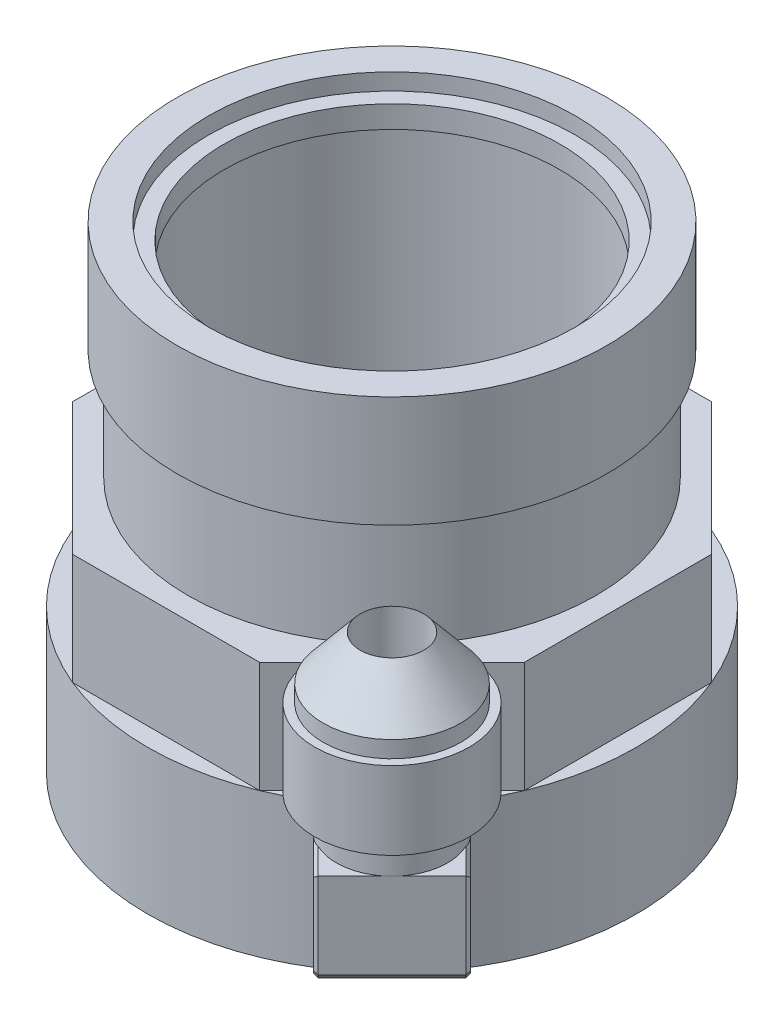
SolidWorks part; units mm, degrees
ref_plane "Спереди" through (0, 0, 0) normal (0, 0, 1) x (1, 0, 0)
ref_plane "Сверху" through (0, 0, 0) normal (0, 1, 0) x (1, 0, 0)
ref_plane "Справа" through (0, 0, 0) normal (1, 0, 0) x (0, 0, -1)
sketch "Эскиз1" plane through (0, 0, 0) normal (0, 1, 0) x (1, 0, 0)
  circle A0 centre (0, 0) radius 22
  dimension "D1" = 44
extrude "Бобышка-Вытянуть1" add sketch "Эскиз1" along normal blind 43 contours A0
sketch "Эскиз3" plane through (0, 43, 0) normal (0, 1, 0) x (1, 0, 0)
  line L0 (0, -1000) -> (0, 49000) construction
  line L1 (20.3253, -8.419) -> (20.3253, 8.419)
  line L2 (20.3253, 8.419) -> (8.419, 20.3253)
  line L3 (8.419, 20.3253) -> (-8.419, 20.3253)
  line L4 (-8.419, 20.3253) -> (-20.3253, 8.419)
  line L5 (-20.3253, 8.419) -> (-20.3253, -8.419)
  line L6 (-20.3253, -8.419) -> (-8.419, -20.3253)
  line L7 (-8.419, -20.3253) -> (8.419, -20.3253)
  line L8 (8.419, -20.3253) -> (20.3253, -8.419)
  circle A0 centre (0, 0) radius 20.3253 construction
  dimension "D1" = 20.3253
extrude "Вырез-Вытянуть1" cut sketch "Эскиз3" against normal blind 30 flip side to cut
sketch "Эскиз4" plane through (0, 43, 0) normal (0, 1, 0) x (1, 0, 0)
  circle A0 centre (0, 0) radius 18.35
  dimension "D1" = 36.7
extrude "Вырез-Вытянуть2" cut sketch "Эскиз4" against normal blind 20 flip side to cut
sketch "Эскиз5" plane through (0, 43, 0) normal (0, 1, 0) x (1, 0, 0)
  circle A0 centre (0, 0) radius 16.5
  dimension "D1" = 33
extrude "Вырез-Вытянуть3" cut sketch "Эскиз5" against normal blind 1.5
sketch "Эскиз6" plane through (0, 43, 0) normal (0, 1, 0) x (1, 0, 0)
  circle A0 centre (0, 0) radius 15.1
  dimension "D1" = 30.2
extrude "Вырез-Вытянуть4" cut sketch "Эскиз6" against normal through all
ref_plane "Плоскость4" through (0, 39.5, 0) normal (0, 1, 0) x (1, 0, 0)
sketch "Эскиз7" plane through (0, 39.5, 0) normal (0, 1, 0) x (1, 0, 0)
  circle A0 centre (0, 0) radius 16.5 construction
  circle A1 centre (0, 0) radius 16.5
extrude "Вырез-Вытянуть5" cut sketch "Эскиз7" against normal blind 27
sketch "Эскиз8" plane through (0, 0, 0) normal (0, -1, 0) x (1, 0, 0)
  circle A0 centre (0, 0) radius 16.65
  dimension "D1" = 33.3
extrude "Вырез-Вытянуть6" cut sketch "Эскиз8" against normal blind 10.5
hole_wizard "Отверстие обработанное метчиком M39x2.02" positions "Эскиз12" profile "Эскиз13" tap size "M39x2.0" standard "Ansi Metric"
sketch "Эскиз12" plane through (0, 0, 0) normal (0, -1, 0) x (-1, 0, 0)
  point P0 (0, 0)
sketch "Эскиз13" plane through (0, 0, 0) normal (1, 0, 0) x (0, 0, -1)
  line L0 (0, 0) -> (0, 20.1159)
  line L1 (0, 20.1159) -> (18.5, 9)
  line L2 (18.5, 9) -> (18.5, 0)
  line L5 (18.5, 0) -> (0, 0)
  line L10 (0, 20.1159) -> (-18.5, 9) construction
  line L11 (0, -6.35) -> (0, 107.95) construction
  dimension "Диаметр сверла" = 37
  dimension "Глубина сверла" = 9
  dimension "Угол заточки сверла" = 118
cosmetic thread "Отверстие резьбы2" parameters "D1"=9, "D2"=39
sketch "Эскиз14" plane through (14.3722, 0, 14.3722) normal (0.7071, 0, 0.7071) x (0.7071, 0, -0.7071)
  line L1 (0, -1000) -> (0, 49000) construction
  circle A0 centre (0, 17.35) radius 3.95
  dimension "D1" = 7.9
  dimension "D2" = 13.4
extrude "Бобышка-Вытянуть2" add sketch "Эскиз14" along normal blind 9.6
sketch "Эскиз15" plane through (21.1604, 0, 21.1604) normal (0.7071, 0, 0.7071) x (0.7071, 0, -0.7071)
  line L1 (-5, 13.1) -> (5, 13.1)
  line L2 (-5, 13.1) -> (-5, 21.6)
  line L3 (-5, 21.6) -> (5, 21.6)
  line L4 (5, 13.1) -> (5, 21.6)
  line L5 (-5, 13.1) -> (5, 21.6) construction
  line L6 (-5, 21.6) -> (5, 13.1) construction
  point P0 (0, 17.35)
  dimension "D1" = 10
  dimension "D2" = 8.5
extrude "Бобышка-Вытянуть3" add sketch "Эскиз15" along normal blind 12
chamfer "Фаска1" distance 0.8 angle 45 1 edges at (29.6457, 13.1, 29.6457)
chamfer "Фаска2" distance 0.3 angle 45 6 edges at (33.1812, 17.75, 26.1102) (32.8984, 13.5, 25.8273) (28.6557, 13.1, 21.5847) (26.1102, 17.75, 33.1812) (25.8273, 13.5, 32.8984) (21.5847, 13.1, 28.6557)
sketch "Эскиз18" plane through (0, 21.6, 0) normal (0, 1, 0) x (1, 0, 0)
  line L0 (21.1604, -21.1604) -> (29.6457, -29.6457) construction
  line L1 (24.696, -17.6249) -> (17.6249, -24.696) construction
  line L2 (32.9691, -26.3223) -> (26.3223, -32.9691) construction
  line L3 (32.9691, -25.898) -> (24.696, -17.6249) construction
  circle A0 centre (26.1102, -26.1102) radius 5
extrude "Бобышка-Вытянуть4" add sketch "Эскиз18" along normal blind 3
chamfer "Фаска3" distance 0.3 angle 45 4 edges at (27.1708, 21.6, 20.0998) (31.3074, 21.6, 24.2363) (20.0998, 21.6, 27.1708) (24.2363, 21.6, 31.3074)
sketch "Эскиз19" plane through (0, 24.6, 0) normal (0, 1, 0) x (1, 0, 0)
  circle A0 centre (26.1102, -26.1102) radius 6.95
  dimension "D1" = 13.9
extrude "Бобышка-Вытянуть5" add sketch "Эскиз19" along normal blind 7
sketch "Эскиз21" plane through (0, 31.6, 0) normal (0, 1, 0) x (1, 0, 0)
  circle A0 centre (26.1102, -26.1102) radius 6.2
  circle A1 centre (26.1102, -26.1102) radius 6.95 construction
  dimension "D1" = 12.4
extrude "Бобышка-Вытянуть6" add sketch "Эскиз21" along normal blind 1.5
ref_plane "Плоскость5" through (0, 0, 0) normal (-0.7071, 0, 0.7071) x (0.7071, 0, 0.7071)
sketch "Эскиз22" plane through (0, 0, 0) normal (-0.7071, 0, 0.7071) x (0.7071, 0, 0.7071)
  line L0 (36.9253, 33.1) -> (36.9253, 37.1)
  line L1 (43.1253, 33.1) -> (30.7253, 33.1) construction
  line L2 (36.9253, 37.1) -> (39.7753, 37.1)
  line L3 (39.7753, 37.1) -> (43.1253, 33.1)
  line L4 (43.1253, 33.1) -> (36.9253, 33.1)
  line L5 (36.9253, -966.9) -> (36.9253, 49033.1) construction
  dimension "D1" = 4
  dimension "D2" = 5.7
revolve "Повернуть1" add sketch "Эскиз22" angle 360 about L5
sketch "Эскиз24" plane through (0, 37.1, 0) normal (0, 1, 0) x (1, 0, 0)
  circle A0 centre (26.1102, -26.1102) radius 2.85 construction
  circle A1 centre (26.1102, -26.1102) radius 2.85
extrude "Вырез-Вытянуть7" cut sketch "Эскиз24" against normal blind 22.5
ref_axis "Ось1" through (32.1389, 17.35, 32.1389) along (-0.7071, 0, -0.7071)
sketch "Эскиз25" plane through (14.3722, 0, 14.3722) normal (0.7071, 0, 0.7071) x (0.7071, 0, -0.7071)
  circle A0 centre (0, 17.35) radius 2.85
  dimension "D1" = 5.7
extrude "Вырез-Вытянуть11" cut sketch "Эскиз25" along direction (-0.7071, 0, -0.7071) on the side of the normal up to surface (16.6 mm away) up to face at (26.1102, 14.6, 28.9602)
sketch "Эскиз26" plane through (14.3722, 0, 14.3722) normal (0.7071, 0, 0.7071) x (0.7071, 0, -0.7071)
  circle A0 centre (0, 17.35) radius 2.85 construction
  circle A1 centre (0, 17.35) radius 2.85
extrude "Вырез-Вытянуть12" cut sketch "Эскиз26" against normal up to next
sketch "Эскиз27" plane through (0, 0, 0) normal (-0.7071, 0, 0.7071) x (0.7071, 0, 0.7071)
  line L0 (18.35, 43) -> (19.35, 43)
  line L1 (18.35, 43) -> (-18.35, 43) construction
  line L2 (19.35, 43) -> (19.35, 33)
  line L3 (19.35, 33) -> (18.35, 33)
  line L4 (18.35, 33) -> (18.35, 43)
  point P4 (18.8022, 33)
  point P7 (0, 0)
  point P8 (18.35, 43)
  dimension "D1" = 10
  dimension "D2" = 1
ref_axis "Ось2" through (0, 12.5, 0) along (0, 1, 0)
revolve "Повернуть2" add sketch "Эскиз27" angle 360 about axis through (0, 12.5, 0) along (0, 1, 0)
